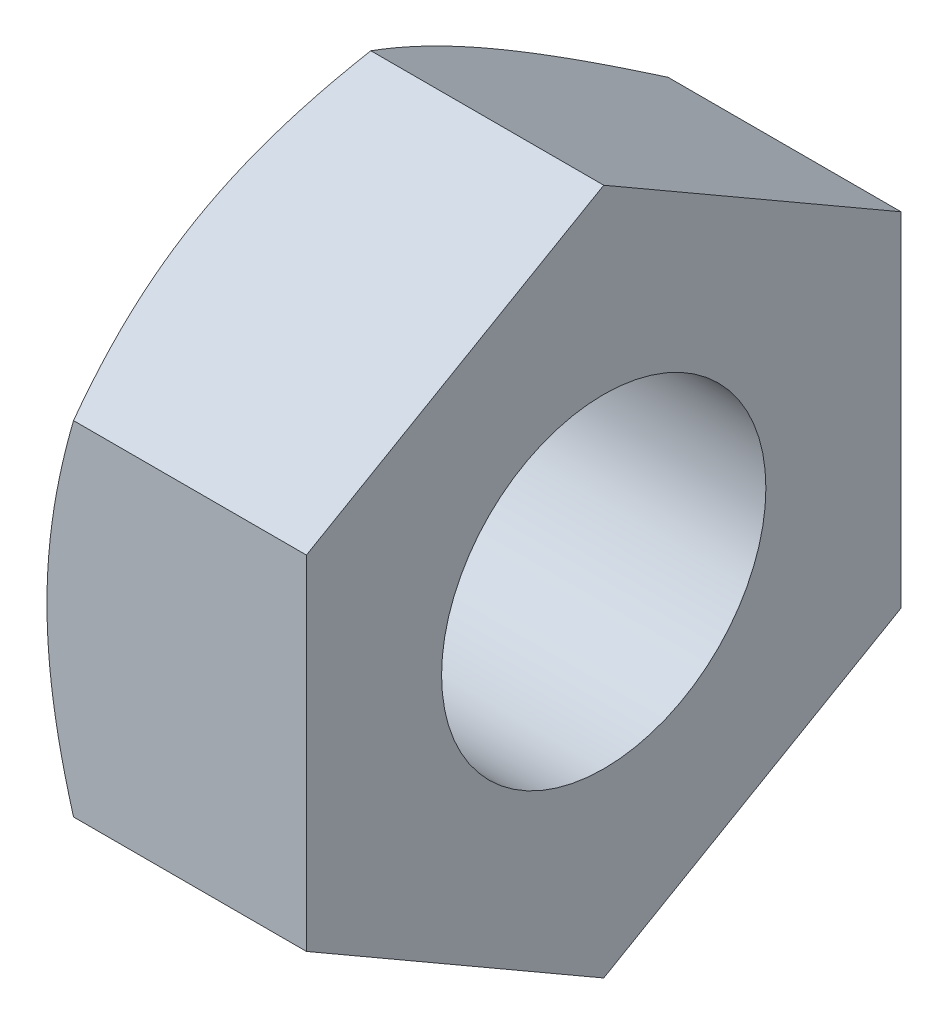
SolidWorks part; units mm, degrees
note: '?' marks a value the reader was unsure of.
ref_plane "Front Plane" through (0, 0, 0) normal (0, 0, 1) x (1, 0, 0)
ref_plane "Top Plane" through (0, 0, 0) normal (0, 1, 0) x (1, 0, 0)
ref_plane "Right Plane" through (0, 0, 0) normal (1, 0, 0) x (0, 0, -1)
ref_axis "Axis_X" through (-2.52, 0, 0) along (1, 0, 0)?
ref_axis "Axis_Y" through (0, 3.493, 0) along (0, -1, 0)?
ref_axis "Axis_Z" through (0, 0, -3.025) along (0, 0, 1)?
ref_plane "Dim.M" through (3, 0, 0) normal (1, 0, 0) x (0, 0, -1)
sketch "Sketch1" plane through (0, 0, 0) normal (1, 0, 0) x (0, 0, -1)
  line L1 (0, 3.1754) -> (-2.75, 1.5877)
  line L2 (-2.75, 1.5877) -> (-2.75, -1.5877)
  line L3 (-2.75, -1.5877) -> (0, -3.1754)
  line L4 (0, -3.1754) -> (2.75, -1.5877)
  line L5 (2.75, -1.5877) -> (2.75, 1.5877)
  line L6 (2.75, 1.5877) -> (0, 3.1754)
  circle A0 centre (0, 0) radius 2.75 construction
  dimension "B" = 5.5
extrude "Boss-Extrude1" add sketch "Sketch1" against normal blind 2.4
sketch "Sketch2" plane through (0, 0, 0) normal (0, 0, 1) x (1, 0, 0)
  line L0 (-2.2385, 0) -> (0.6157, 0) construction
  line L1 (-2.4, 2.75) -> (-2.1544, 3.1754)
  line L2 (-2.4, 3.1754) -> (-2.4, 1.5877) construction
  line L3 (-2.4, 3.1754) -> (0, 3.1754) construction
  line L4 (-2.1544, 3.1754) -> (-2.4, 3.1754)
  line L5 (-2.4, 3.1754) -> (-2.4, 2.75)
  dimension "B" = 5.5
  dimension "FIX_1" = 30
revolve "Cut-Revolve1" cut sketch "Sketch2" about L0
sketch "Sketch5" plane through (0, 0, 0) normal (0, 0, 1) x (1, 0, 0)
  line L0 (-1.2, 2.75) -> (-0.9544, 3.1754)
  line L3 (-0.9544, 3.1754) -> (-1.2, 3.1754)
  line L4 (-1.2, 3.1754) -> (-1.2, 2.75) construction
  line L5 (0, 2.75) -> (-0.2456, 3.1754)
  line L6 (0, 3.1754) -> (0, 1.5877) construction
  line L7 (-0.2456, 3.1754) -> (0, 3.1754)
  line L8 (0, 3.1754) -> (0, 2.75)
  line L9 (-1.687, 0) -> (0.4573, 0) construction
  line L10 (-1.2, 3.1754) -> (-6.2, 3.1754)
  line L11 (-6.2, 3.1754) -> (-6.2, 0)
  line L12 (-6.2, 0) -> (-1.2, 0)
  line L13 (-1.2, 0) -> (-1.2, 2.75)
  dimension "D1" = 5
  dimension "B" = 5.5
  dimension "T1" = 1.2
revolve "Cut-Revolve2" [suppressed] cut sketch "Sketch5" about L9
hole_wizard "Tap2" [suppressed] positions "Sketch6" profile "Sketch7" hole size "M1.6x0.35" standard "JIS"
sketch "Sketch6" plane through (0, 0, 0) normal (1, 0, 0) x (0, 0, -1)
  point P0 (0, 0)
sketch "Sketch7" plane through (0, 0, 0) normal (0, 1, 0) x (0, 0, -1)
  line L0 (0, 0) -> (0, 1.2)
  line L1 (0, 1.2) -> (0.7835, 1.2)
  line L2 (0.7835, 1.2) -> (0.7835, 0)
  line L5 (0.7835, 0) -> (0, 0)
  line L11 (0, 0) -> (0, 1.2) construction
  dimension "Thru Hole Depth" = 1.2
  dimension "HSD_1" = 2.459
sketch "Sketch8" plane through (0, 0, 0) normal (1, 0, 0) x (0, 0, -1)
  circle A0 centre (0, 0) radius 1.5
  dimension "D1" = 3
extrude "Cut-Extrude1" cut sketch "Sketch8" against normal through all
equation "\"Factor\"= 1.082532"
equation "\"Pitch_M\"= IIF ( \"M\" = 24 , 3 , IIF ( \"M\" = 20 , 2.5 , IIF ( \"M\" = 16 , 2 , IIF ( \"M\" = 12 , 1.75 , IIF ( \"M\" = 10 , 1.5 , IIF ( \"M\" = 8 , 1.25 , IIF ( \"M\" = 6 , 1 , IIF ( \"M\" = 5 , 0.8 , IIF ( \"M\" = 4 , 0.7 , IIF ( \"M\" = 3 , 0.5 , IIF ( \"M\" = 2.6 , 0.45 , IIF ( \"M\" = 2.5 , 0.45 , IIF ( \"M\" = 2 , 0.4 , 0.4 ) ) ) ) ) ) ) ) ) ) ) ) )"
equation "\"HSD_1\"= round ( \"M\" - \"Factor\" * \"Pitch_M\" , 3 )"
